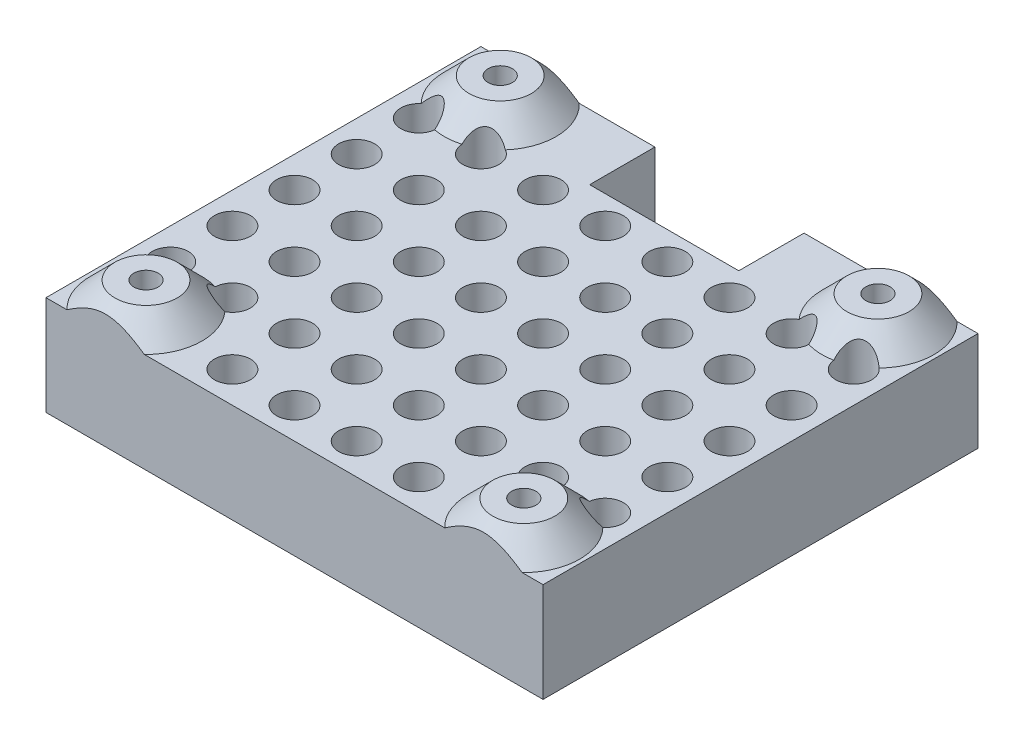
SolidWorks part; units mm, degrees
ref_plane "Front Plane" through (0, 0, 0) normal (0, 0, 1) x (1, 0, 0)
ref_plane "Top Plane" through (0, 0, 0) normal (0, 1, 0) x (1, 0, 0)
ref_plane "Right Plane" through (0, 0, 0) normal (1, 0, 0) x (0, 0, -1)
sketch "Sketch1" plane through (0, 0, 0) normal (0, 1, 0) x (1, 0, 0)
  line L1 (-20, 17.5) -> (20, 17.5)
  line L2 (-20, 17.5) -> (-20, -17.5)
  line L3 (-20, -17.5) -> (20, -17.5)
  line L4 (20, 17.5) -> (20, -17.5)
  line L5 (-20, 17.5) -> (20, -17.5) construction
  line L6 (-20, -17.5) -> (20, 17.5) construction
  point P0 (0, 0)
  dimension "D1" = 40
  dimension "D2" = 35
extrude "Boss-Extrude1" add sketch "Sketch1" along normal blind 8
sketch "Sketch5" plane through (0, 0, 0) normal (0, -1, 0) x (1, 0, 0)
  circle A0 centre (-17.5, 15) radius 1.45
  dimension "D1" = 2.9
  dimension "D2" = 17.5
  dimension "D3" = 15
extrude "Cut-Extrude3" cut sketch "Sketch5" against normal through all
pattern_linear "LPattern1" count 8 spacing 5 along (1, 0, 0) count 7 spacing 5 along (0, 0, -1) skipping (0, 6), (1, 0), (1, 6), (2, 6), (3, 6), (4, 6), (5, 6), (6, 0), (6, 6), (7, 0), (7, 6) of "Cut-Extrude3"
sketch "Sketch2" plane through (0, 8, 0) normal (0, 1, 0) x (1, 0, 0)
  line L1 (15.2, -14.25) -> (-15.2, -14.25) construction
  line L2 (15.2, -14.25) -> (15.2, 14.25) construction
  line L3 (15.2, 14.25) -> (-15.2, 14.25) construction
  line L4 (-15.2, -14.25) -> (-15.2, 14.25) construction
  line L5 (15.2, -14.25) -> (-15.2, 14.25) construction
  line L6 (15.2, 14.25) -> (-15.2, -14.25) construction
  circle A0 centre (-15.2, 14.25) radius 2.5
  circle A1 centre (15.2, 14.25) radius 2.5
  circle A2 centre (15.2, -14.25) radius 2.5
  circle A3 centre (-15.2, -14.25) radius 2.5
  point P2 (0, 0)
  dimension "D3" = 5
  dimension "D1" = 30.4
  dimension "D2" = 28.5
extrude "Boss-Extrude2" add sketch "Sketch2" along normal blind 2 and the other way up to surface (8 mm away) other way up to face at (-7.5, 0, 13.55)
sketch "Sketch6" plane through (0, 8, 0) normal (0, 1, 0) x (1, 0, 0)
  circle A1 centre (-17.5, -15) radius 1.45
  circle A2 centre (-17.5, -15) radius 1.45
  dimension "D1" = 0
extrude "Boss-Extrude3" add sketch "Sketch6" against normal up to surface (8 mm away) up to face at (-7.5, 0, 13.55)
sketch "Sketch3" plane through (0, 10, 0) normal (0, 1, 0) x (1, 0, 0)
  circle A0 centre (-15.2, 14.25) radius 0.975
  circle A1 centre (15.2, 14.25) radius 0.975
  circle A2 centre (-15.2, -14.25) radius 0.975
  circle A3 centre (15.2, -14.25) radius 0.975
  dimension "D1" = 1.95
extrude "Cut-Extrude1" cut sketch "Sketch3" against normal through all
sketch "Sketch4" plane through (0, 8, 0) normal (0, 1, 0) x (1, 0, 0)
  line L0 (20, 17.5) -> (-20, 17.5) construction
  line L1 (6, 12.25) -> (-6, 12.25)
  line L2 (6, 12.25) -> (6, 17.5)
  line L3 (6, 17.5) -> (-6, 17.5)
  line L4 (-6, 12.25) -> (-6, 17.5)
  line L5 (6, 12.25) -> (-6, 17.5) construction
  line L6 (6, 17.5) -> (-6, 12.25) construction
  point P0 (0, 14.875)
  point P7 (-15.2, 14.25)
  dimension "D1" = 12
  dimension "D2" = 2
extrude "Cut-Extrude2" cut sketch "Sketch4" against normal through all
chamfer "Chamfer1" distance 2 angle 45 4 edges at (15.2, 8, -11.75) (15.2, 8, 16.75) (-15.2, 8, 16.75) (-15.2, 8, -11.75)
